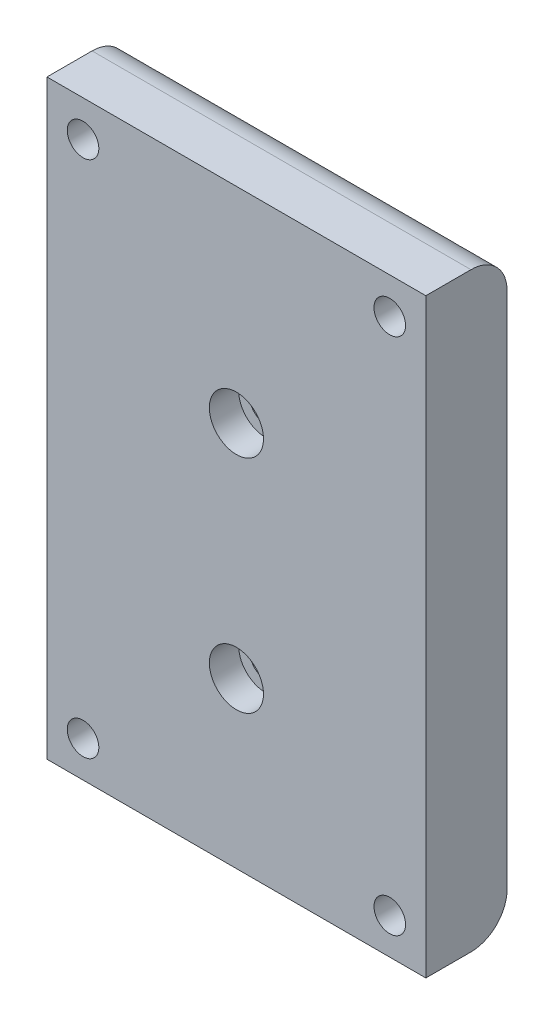
SolidWorks part; units mm, degrees
ref_plane "Front Plane" through (0, 0, 0) normal (0, 0, 1) x (1, 0, 0)
ref_plane "Top Plane" through (0, 0, 0) normal (0, 1, 0) x (1, 0, 0)
ref_plane "Right Plane" through (0, 0, 0) normal (1, 0, 0) x (0, 0, -1)
sketch "Sketch1" plane through (0, 0, 0) normal (0, 0, 1) x (1, 0, 0)
  line L1 (0, 0) -> (42, 0)
  line L2 (0, 0) -> (0, 65.5)
  line L3 (0, 65.5) -> (42, 65.5)
  line L4 (42, 0) -> (42, 65.5)
  dimension "D1" = 42
  dimension "D2" = 65.5
extrude "Boss-Extrude1" add sketch "Sketch1" along normal blind 9
sketch "Sketch2" plane through (0, 0, 0) normal (0, 0, -1) x (-1, 0, 0)
  line L0 (-42, 32.75) -> (0, 32.75) construction
  line L1 (-42, 0) -> (-42, 65.5) construction
  line L2 (0, 65.5) -> (0, 0) construction
  line L3 (-42, 42.75) -> (0, 42.75) construction
  line L4 (-21, 42.75) -> (-21, 18.25) construction
  line L5 (-25.5, 18.25) -> (-25.5, 32.0846)
  line L6 (-16.5, 18.25) -> (-16.5, 32.0846)
  arc A0 (-14.5556, 38.0098) -> (-27.4444, 38.0098) centre (-21, 42.75) ccw
  arc A1 (-25.5, 18.25) -> (-16.5, 18.25) centre (-21, 18.25) ccw
  arc A2 (-16.5, 32.0846) -> (-14.5556, 38.0098) centre (-6.5, 32.0846) cw
  arc A3 (-25.5, 32.0846) -> (-27.4444, 38.0098) centre (-35.5, 32.0846) ccw
  point P11 (-21, 42.75)
  dimension "D2" = 16
  dimension "D3" = 9
  dimension "D5" = 10
  dimension "D4" = 24.5
  dimension "D1" = 10
extrude "Cut-Extrude2" cut sketch "Sketch2" against normal blind 4.5
sketch "Sketch3" plane through (0, 0, 4.5) normal (0, 0, -1) x (-1, 0, 0)
  line L0 (-21, 42.75) -> (-21, 22.25) construction
  line L1 (-21, 22.25) -> (-21, 18.25) construction
  line L2 (-24, 18.25) -> (-24, 22.25)
  line L3 (-18, 22.25) -> (-18, 18.25)
  arc A0 (-18, 22.25) -> (-24, 22.25) centre (-21, 22.25) ccw
  arc A1 (-24, 18.25) -> (-18, 18.25) centre (-21, 18.25) ccw
  circle A2 centre (-21, 22.25) radius 1.75
  circle A3 centre (-21, 18.25) radius 1.75
  circle A4 centre (-21, 42.75) radius 1.75
  dimension "D2" = 6
  dimension "D4" = 3.5
  dimension "D5" = 3.5
  dimension "D1" = 20.5
  dimension "D3" = 4
extrude "Cut-Extrude5" cut sketch "Sketch3" against normal through all contours A3 | A4 region at (21, 18.25, 4.5) region at (21, 42.75, 4.5)
sketch "Sketch5" plane through (0, 0, 9) normal (0, 0, 1) x (1, 0, 0)
  circle A0 centre (21, 18.25) radius 3
  circle A1 centre (21, 42.75) radius 3
  dimension "D1" = 6
extrude "Cut-Extrude6" cut sketch "Sketch5" against normal blind 3.25
fillet "Fillet1" radius 4 2 edges at (21, 0, 0) (21, 65.5, 0)
sketch "Sketch6" plane through (0, 0, 0) normal (0, 0, -1) x (-1, 0, 0)
  line L0 (-4, 61.5) -> (-4, 4) construction
  line L1 (-42, 65.5) -> (0, 65.5) construction
  line L2 (-42, 65.5) -> (-42, 0) construction
  line L3 (-42, 0) -> (0, 0) construction
  line L4 (0, 65.5) -> (0, 0) construction
  line L5 (-38, 4) -> (-4, 4) construction
  line L6 (-38, 61.5) -> (-38, 4) construction
  line L7 (-38, 61.5) -> (-4, 61.5) construction
  circle A0 centre (-38, 61.5) radius 1.75
  circle A1 centre (-4, 61.5) radius 1.75
  circle A2 centre (-4, 4) radius 1.75
  circle A3 centre (-38, 4) radius 1.75
  line M16 (-42, 4) -> (0, 4)
  dimension "D2" = 3.5
  dimension "D1" = 4
extrude "Cut-Extrude7" cut sketch "Sketch6" against normal through all contours A2 M16 | A2 M16 | A3 M16 | A3 M16 | A0 | A1 region at (4, 4.7427, 0) region at (38, 3.2573, 0) region at (38, 4.7427, 0) region at (4, 3.2573, 0)
sketch "Sketch7" plane through (0, 0, 0) normal (0, 0, -1) x (-1, 0, 0)
  circle A0 centre (-38, 61.5) radius 3
  circle A1 centre (-4, 61.5) radius 3
  circle A2 centre (-4, 4) radius 3
  circle A3 centre (-38, 4) radius 3
  dimension "D1" = 6
extrude "Cut-Extrude8" cut sketch "Sketch7" against normal blind 3
